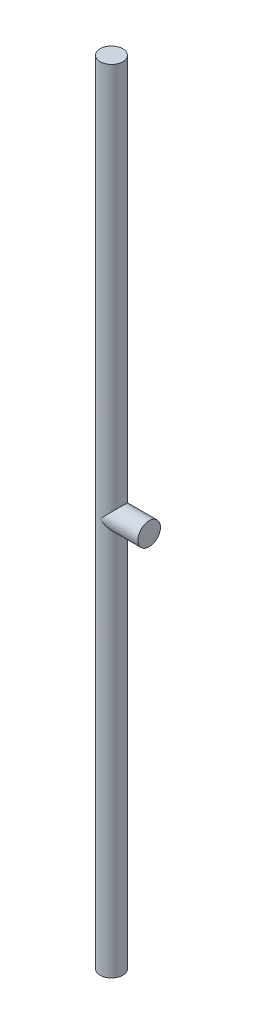
SolidWorks part; units mm, degrees
ref_plane "Front Plane" through (0, 0, 0) normal (0, 0, 1) x (1, 0, 0)
ref_plane "Top Plane" through (0, 0, 0) normal (0, 1, 0) x (1, 0, 0)
ref_plane "Right Plane" through (0, 0, 0) normal (1, 0, 0) x (0, 0, -1)
sketch "Sketch8" plane through (0, 0, 0) normal (0, 1, 0) x (1, 0, 0)
  circle A0 centre (0, 0) radius 150
  dimension "D1" = 300
extrude "Boss-Extrude1" add sketch "Sketch8" along normal blind 5250 and the other way blind 5250
sketch "Sketch9" plane through (0, 0, 0) normal (1, 0, 0) x (0, 0, -1)
  circle A0 centre (0, 0) radius 150
  dimension "D1" = 300
extrude "Boss-Extrude2" add sketch "Sketch9" along normal blind 500
